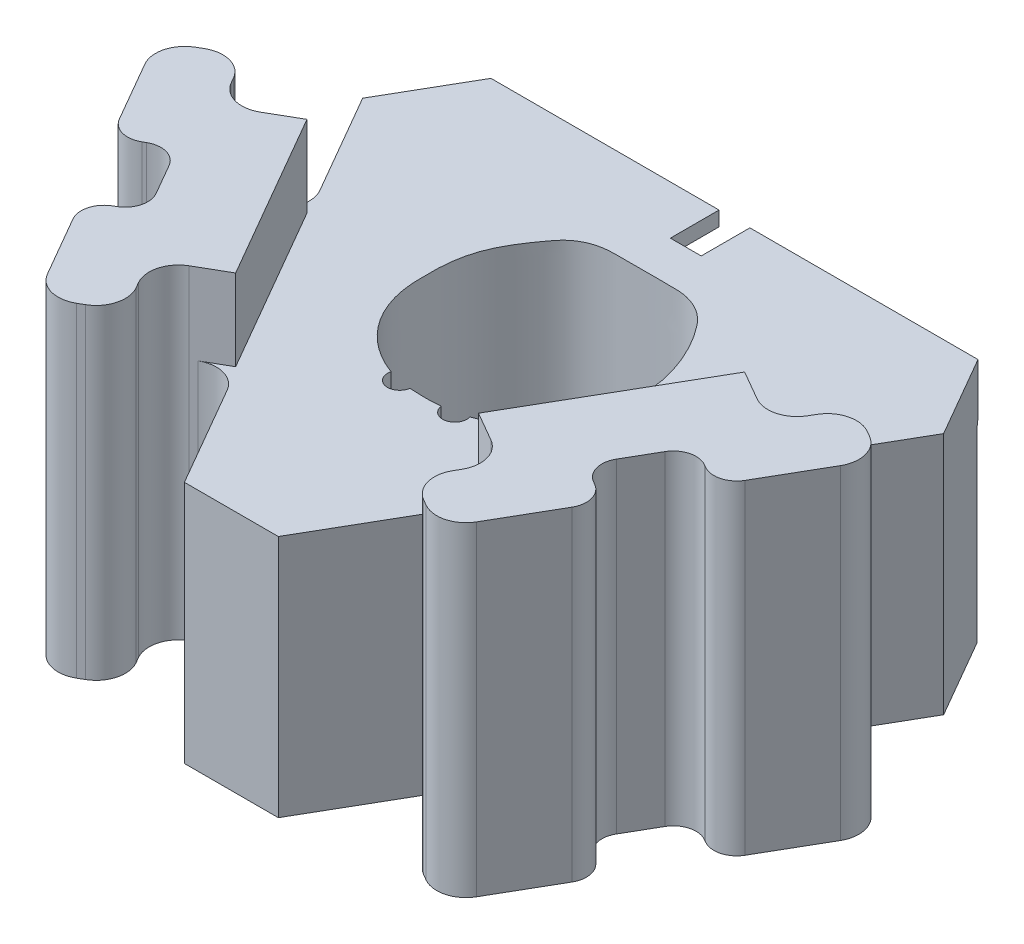
SolidWorks part; units mm, degrees
material "Nylon 101"
ref_plane "Plan de face" through (0, 0, 0) normal (0, 0, 1) x (1, 0, 0)
ref_plane "Plan de dessus" through (0, 0, 0) normal (0, 1, 0) x (1, 0, 0)
ref_plane "Plan de droite" through (0, 0, 0) normal (1, 0, 0) x (0, 0, -1)
sketch "Esquisse2" plane through (0, 0, 0) normal (0, 1, 0) x (1, 0, 0)
  line L5 (0, 0) -> (0, 12) construction
  line L6 (15, 12) -> (-15, 12)
  line L10 (2.8923, -18.9904) -> (17.8923, 6.9904)
  line L11 (0, 0) -> (10.3923, -6) construction
  line L12 (-17.8923, 6.9904) -> (-2.8923, -18.9904)
  line L13 (0, 0) -> (-10.3923, -6) construction
  line L14 (-15, 12) -> (-17.8923, 6.9904)
  line L15 (-2.8923, -18.9904) -> (2.8923, -18.9904)
  line L16 (17.8923, 6.9904) -> (15, 12)
  circle A0 centre (0, 0) radius 6.4543 construction
  spline S0 degree 3 poles (-6.4916, -0.6583) (-6.5698, 2.1101) (-5.6306, 3.6458) (-3.9015, 5.9899) (-2.756, 6.4428) (-0.8765, 6.4556) (1.1323, 6.4563) (2.7646, 6.4372) (3.9155, 5.9368) (5.686, 3.7258) (6.557, 1.3673) (6.4965, -0.4633) (6.5146, -1.1319) (6.2478, -3.8936) (4.3275, -6.6394) (0.5445, -7.077) (-0.4227, -7.0644) (-3.089, -6.9353) (-6.1206, -4.861) (-6.5148, -1.2298) (-6.4916, -0.6583) (-6.5698, 2.1101) (-5.6306, 3.6458) knots -0.028087 -0.008777 -0.000975 0 0.112372 0.130276 0.173621 0.187169 0.252205 0.26694 0.319781 0.34342 0.479691 0.498677 0.514296 0.542967 0.756721 0.785787 0.80456 0.825241 0.971913 0.991223 0.999025 1 1.112372 1.130276 1.173621 only from (-6.4978, -0.4355) to (-6.4978, -0.4355)
  point P6 (0, 12)
  point P15 (0, 0)
  dimension "D1" = 30
  dimension "D2" = 3
  dimension "D3" = 12
extrude "Boss.-Extru.1" add sketch "Esquisse2" along normal blind 15
sketch "Esquisse3" plane through (0, 0, 0) normal (0, 1, 0) x (1, 0, 0)
  line L0 (0, 0) -> (3.3, 0) construction
  line L1 (0, 0) -> (0, 3.3) construction
  line L2 (-16.4462, 9.4952) -> (0, 0) construction
  line L5 (-17.8923, 6.9904) -> (-15, 12) construction
  line L6 (0, 0) -> (16.4462, 9.4952) construction
  line L7 (15, 12) -> (17.8923, 6.9904) construction
  line L8 (0, 0) -> (0, -18.9904) construction
  line L9 (2.8923, -18.9904) -> (-2.8923, -18.9904) construction
  circle A0 centre (0, 0) radius 3.3 construction
  circle A5 centre (-12.9821, 7.4952) radius 2
  circle A7 centre (12.9821, 7.4952) radius 2
  circle A8 centre (0, -14.9904) radius 2
  point P23 (0, 0)
  dimension "D1" = 6.6
  dimension "D3" = 4
  dimension "D2" = 4
  dimension "D4" = 3
extrude "Enlèv. mat.-Extru.3" [suppressed] cut sketch "Esquisse3" against normal blind 8 and the other way through all from surface
sketch "Esquisse4" plane through (0, 0, 0) normal (0, 0, 1) x (1, 0, 0)
  line L0 (0, 0) -> (0, 7) construction
  line L1 (11, 3) -> (-11, 3) construction
  line L2 (11, 3) -> (11, 11) construction
  line L3 (11, 11) -> (-11, 11) construction
  line L4 (-11, 3) -> (-11, 11) construction
  line L5 (11, 3) -> (-11, 11) construction
  line L6 (11, 11) -> (-11, 3) construction
  line L8 (-17.8923, 0) -> (-2.8923, 0) construction
  circle A0 centre (-11, 11) radius 1.5
  circle A1 centre (11, 11) radius 1.5
  circle A2 centre (11, 3) radius 1.5
  circle A3 centre (-11, 3) radius 1.5
  point P0 (0, 7)
  dimension "D4" = 3
  dimension "D1" = 8
  dimension "D2" = 22
  dimension "D3" = 3
extrude "Enlèv. mat.-Extru.4" cut sketch "Esquisse4" along normal blind 8 from surface starting at face at (0, 7.5, -12)
sketch "Esquisse5" plane through (0, 0, 0) normal (0, 1, 0) x (1, 0, 0)
  line L0 (0, 0) -> (0, -18.9904) construction
  line L1 (2.8923, -18.9904) -> (-2.8923, -18.9904) construction
  line L2 (10.3923, -6) -> (17.3205, -10) construction
  line L3 (17.8923, 6.9904) -> (2.8923, -18.9904) construction
  line L4 (13.2205, -17.1014) -> (15.3705, -13.3775)
  line L5 (20.7617, -0.4397) -> (20.4153, -0.2397)
  line L6 (17.9564, -0.8986) -> (17.7564, -1.245)
  line L7 (15.2976, -1.9038) -> (13.3923, -0.8038)
  line L8 (13.3923, -0.8038) -> (7.3923, -11.1962)
  line L9 (9.2976, -12.2962) -> (7.3923, -11.1962)
  line L10 (9.7564, -15.1014) -> (9.9564, -14.755)
  line L11 (10.7617, -17.7603) -> (10.4153, -17.5603)
  line L12 (20.7617, -0.4397) -> (20.4153, -0.2397)
  line L13 (17.9564, -0.8986) -> (17.7564, -1.245)
  line L14 (15.2976, -1.9038) -> (13.3923, -0.8038)
  line L15 (9.2976, -12.2962) -> (7.3923, -11.1962)
  line L16 (9.7564, -15.1014) -> (9.9564, -14.755)
  line L17 (10.7617, -17.7603) -> (10.4153, -17.5603)
  line L18 (-17.3205, -10) -> (-18.5705, -7.8349) construction
  line L19 (-16.0705, -12.1651) -> (-17.3205, -10) construction
  line L20 (-10.3923, -6) -> (-17.3205, -10) construction
  line L21 (-19.2705, -6.6225) -> (-21.4205, -2.8986)
  line L22 (-17.1849, -7.0349) -> (-17.3581, -7.1349)
  line L23 (-14.1724, -9.4526) -> (-15.2724, -7.5474)
  line L24 (-14.8581, -11.4651) -> (-14.6849, -11.3651)
  line L25 (-10.7617, -17.7603) -> (-10.4153, -17.5603)
  line L26 (-9.7564, -15.1014) -> (-9.9564, -14.755)
  line L27 (-9.2976, -12.2962) -> (-7.3923, -11.1962)
  line L28 (-15.2976, -1.9038) -> (-13.3923, -0.8038)
  line L29 (-17.9564, -0.8986) -> (-17.7564, -1.245)
  line L30 (-20.7617, -0.4397) -> (-20.4153, -0.2397)
  line L31 (-10.7617, -17.7603) -> (-10.4153, -17.5603)
  line L32 (-9.7564, -15.1014) -> (-9.9564, -14.755)
  line L33 (14.8581, -11.4651) -> (14.6849, -11.3651)
  line L34 (14.1724, -9.4526) -> (15.2724, -7.5474)
  line L35 (17.1849, -7.0349) -> (17.3581, -7.1349)
  line L36 (16.0705, -12.1651) -> (17.3205, -10) construction
  line L37 (19.2705, -6.6225) -> (21.4205, -2.8986)
  line L38 (17.3205, -10) -> (18.5705, -7.8349) construction
  line L39 (-9.2976, -12.2962) -> (-7.3923, -11.1962)
  line L40 (-13.3923, -0.8038) -> (-7.3923, -11.1962)
  line L41 (-15.2976, -1.9038) -> (-13.3923, -0.8038)
  line L42 (-17.9564, -0.8986) -> (-17.7564, -1.245)
  line L43 (-20.7617, -0.4397) -> (-20.4153, -0.2397)
  line L44 (-13.2205, -17.1014) -> (-15.3705, -13.3775)
  arc A0 (10.7617, -17.7603) -> (13.2205, -17.1014) centre (11.6617, -16.2014) ccw
  arc A1 (9.7564, -15.1014) -> (10.4153, -17.5603) centre (11.3153, -16.0014) ccw
  arc A2 (9.2976, -12.2962) -> (9.9564, -14.755) centre (8.3976, -13.855) cw
  arc A3 (21.4205, -2.8986) -> (20.7617, -0.4397) centre (19.8617, -1.9986) ccw
  arc A4 (17.7564, -1.245) -> (15.2976, -1.9038) centre (16.1976, -0.345) cw
  arc A5 (20.4153, -0.2397) -> (17.9564, -0.8986) centre (19.5153, -1.7986) ccw
  arc A6 (10.4153, -17.5603) -> (9.7564, -15.1014) centre (11.3153, -16.0014) cw
  arc A7 (9.9564, -14.755) -> (9.2976, -12.2962) centre (8.3976, -13.855) ccw
  arc A8 (13.2205, -17.1014) -> (10.7617, -17.7603) centre (11.6617, -16.2014) cw
  arc A9 (15.2976, -1.9038) -> (17.7564, -1.245) centre (16.1976, -0.345) ccw
  arc A10 (17.9564, -0.8986) -> (20.4153, -0.2397) centre (19.5153, -1.7986) cw
  arc A11 (20.7617, -0.4397) -> (21.4205, -2.8986) centre (19.8617, -1.9986) cw
  arc A24 (17.3581, -7.1349) -> (19.2705, -6.6225) centre (18.0581, -5.9225) ccw
  arc A25 (15.2724, -7.5474) -> (17.1849, -7.0349) centre (16.4849, -8.2474) cw
  arc A26 (14.6849, -11.3651) -> (14.1724, -9.4526) centre (15.3849, -10.1526) cw
  arc A27 (14.8581, -11.4651) -> (15.3705, -13.3775) centre (14.1581, -12.6775) cw
  arc A28 (-14.8581, -11.4651) -> (-15.3705, -13.3775) centre (-14.1581, -12.6775) ccw
  arc A29 (-14.6849, -11.3651) -> (-14.1724, -9.4526) centre (-15.3849, -10.1526) ccw
  arc A30 (-15.2724, -7.5474) -> (-17.1849, -7.0349) centre (-16.4849, -8.2474) ccw
  arc A31 (-17.3581, -7.1349) -> (-19.2705, -6.6225) centre (-18.0581, -5.9225) cw
  arc A32 (-20.7617, -0.4397) -> (-21.4205, -2.8986) centre (-19.8617, -1.9986) ccw
  arc A33 (-17.9564, -0.8986) -> (-20.4153, -0.2397) centre (-19.5153, -1.7986) ccw
  arc A34 (-15.2976, -1.9038) -> (-17.7564, -1.245) centre (-16.1976, -0.345) cw
  arc A35 (-13.2205, -17.1014) -> (-10.7617, -17.7603) centre (-11.6617, -16.2014) ccw
  arc A36 (-9.9564, -14.755) -> (-9.2976, -12.2962) centre (-8.3976, -13.855) cw
  arc A37 (-10.4153, -17.5603) -> (-9.7564, -15.1014) centre (-11.3153, -16.0014) ccw
  arc A38 (-20.4153, -0.2397) -> (-17.9564, -0.8986) centre (-19.5153, -1.7986) cw
  arc A39 (-17.7564, -1.245) -> (-15.2976, -1.9038) centre (-16.1976, -0.345) ccw
  arc A40 (-21.4205, -2.8986) -> (-20.7617, -0.4397) centre (-19.8617, -1.9986) cw
  arc A41 (-9.2976, -12.2962) -> (-9.9564, -14.755) centre (-8.3976, -13.855) ccw
  arc A42 (-9.7564, -15.1014) -> (-10.4153, -17.5603) centre (-11.3153, -16.0014) cw
  arc A43 (-10.7617, -17.7603) -> (-13.2205, -17.1014) centre (-11.6617, -16.2014) cw
  point P19 (12.3205, -18.6603)
  point P22 (8.8564, -16.6603)
  point P25 (10.8564, -13.1962)
  point P28 (22.3205, -1.3397)
  point P31 (16.8564, -2.8038)
  point P34 (18.8564, 0.6603)
  point P64 (14.7224, -8.5)
  point P72 (15.9724, -6.3349)
  point P75 (13.4724, -10.6651)
  point P88 (-13.4724, -10.6651)
  point P89 (-15.9724, -6.3349)
  point P90 (-18.8564, 0.6603)
  point P91 (-16.8564, -2.8038)
  point P92 (-22.3205, -1.3397)
  point P93 (-10.8564, -13.1962)
  point P94 (-8.8564, -16.6603)
  point P95 (-12.3205, -18.6603)
  dimension "D5" = 1.8
  dimension "D8" = 1.4
  dimension "D1" = 8
  dimension "D2" = 4
  dimension "D3" = 4
  dimension "D4" = 10
  dimension "D6" = 3
  dimension "D7" = 5
extrude "Boss.-Extru.2" add sketch "Esquisse5" against normal up to surface and the other way blind 5 from surface contours L5 A5 L6 A4 L7 L8 L9 A2 L10 A1 L11 A0 L4 A3 | L25 A37 L26 A36 L27 L40 L28 A34 L29 A33 L30 A32 L21 A31 L22 A30 L23 A29 L24 A28 L44 A35 region at (13.999, 0, 8.0823) region at (-13.999, 0, 8.0823) up to face at (0, 0, 0) starting at face at (0, 15, 0)
fillet "Congé5" radius 1.8 4 edges at (13.3923, 7.5, 0.8038) (7.3923, 7.5, 11.1962) (-7.3923, 7.5, 11.1962) (-13.3923, 7.5, 0.8038)
sketch "Esquisse6" plane through (0, 0, 0) normal (0, 1, 0) x (1, 0, 0)
  line L0 (-13.3923, -0.8038) -> (-7.3923, -11.1962)
  line L1 (-7.3923, -11.1962) -> (-7.4789, -11.2462)
  line L2 (-7.3923, -11.1962) -> (-9.2976, -12.2962) construction
  line L3 (-7.4789, -11.2462) -> (-13.4789, -0.8538)
  line L4 (-13.3923, -0.8038) -> (-15.2976, -1.9038) construction
  line L5 (-13.4789, -0.8538) -> (-13.3923, -0.8038)
  line L6 (7.3923, -11.1962) -> (13.3923, -0.8038)
  line L7 (13.3923, -0.8038) -> (13.4789, -0.8538)
  line L8 (14.9512, -1.7038) -> (13.3923, -0.8038) construction
  line L9 (13.4789, -0.8538) -> (7.4789, -11.2462)
  line L10 (7.3923, -11.1962) -> (9.2976, -12.2962) construction
  line L11 (7.4789, -11.2462) -> (7.3923, -11.1962)
  dimension "D1" = 0.1
  dimension "D2" = 0.1
extrude "Enlèv. mat.-Extru.5" cut sketch "Esquisse6" along normal up to surface (20 mm away) from surface up to face at (-14.8463, 20, 8.5715) starting at face at (0, 15, 4.1586)
sketch "Esquisse7" plane through (0, 0, -12) normal (0, 0, -1) x (-1, 0, 0)
  line L0 (15, 15) -> (15, 0) construction
  line L1 (-15, 0) -> (15, 0) construction
  line L2 (-15, 0) -> (-15, 14) construction
  line L3 (-15, 14) -> (-0.85, 14) construction
  line L4 (15, 0) -> (15, 14) construction
  line L5 (-15, 15) -> (15, 15) construction
  line L6 (0.85, 0) -> (-0.85, 0)
  line L7 (0.85, 14) -> (0.85, 15) construction
  line L8 (0.85, 15) -> (-0.85, 15) construction
  line L9 (-0.85, 14) -> (-0.85, 15) construction
  line L10 (-0.85, 0) -> (-0.85, 14) construction
  line L11 (0.85, 0) -> (0.85, 14) construction
  line L12 (-0.85, 14) -> (0.85, 14) construction
  line L13 (0.85, 14) -> (15, 14) construction
  line L14 (-15.1, -0.1) -> (-15.1, 14.1)
  line L15 (-15.1, 14.1) -> (-0.95, 14.1)
  line L16 (-0.95, 14.1) -> (-0.95, 15.1)
  line L17 (0.95, 15.1) -> (-0.95, 15.1)
  line L18 (0.95, 14.1) -> (0.95, 15.1)
  line L19 (0.95, 14.1) -> (15.1, 14.1)
  line L20 (15.1, -0.1) -> (15.1, 14.1)
  line L21 (-15.1, -0.1) -> (15.1, -0.1)
  circle A0 centre (11, 11) radius 1.5 construction
  circle M9 centre (-11, 3) radius 1.5
  circle M10 centre (11, 11) radius 1.5
  circle M11 centre (11, 3) radius 1.5
  circle M12 centre (-11, 11) radius 1.5
  line M13 (-15, 0) -> (15, 0)
  line M14 (15, 0) -> (15, 15)
  line M15 (15, 15) -> (-15, 15)
  line M16 (-15, 15) -> (-15, 0)
  dimension "D1" = 3
  dimension "D2" = 0.85
  dimension "D3" = 0.85
  dimension "D4" = 0.1
extrude "Enlèv. mat.-Extru.6" cut sketch "Esquisse7" against normal blind 3 contours L14 L21 L20 L19 L15 M14 M13 M16 | L19 L18 L16 L15 M15 M16 M13 M14 M10 M12 M11 M9 | L18 L17 L16 M15 region at (-7.925, -0.0334, -12) region at (0, 7.0859, -12) region at (0, 15.05, -12)
fillet "Congé6" radius 3 2 edges at (-15.1, 14.1, -10.4134) (15.1, 14.1, -10.4134)
sketch "Esquisse8" plane through (0, 15, 0) normal (0, 1, 0) x (1, 0, 0)
  line L0 (0, 0) -> (0, -2.8854) construction
  circle A0 centre (-1.7, -6.9242) radius 0.75
  circle A1 centre (1.7, -6.9242) radius 0.75
  spline S0 degree 3 poles (-5.6306, 3.6458) (-6.5698, 2.1101) (-6.4916, -0.6583) (-6.5148, -1.2298) (-6.1206, -4.861) (-3.089, -6.9353) (-0.4227, -7.0644) (0.5445, -7.077) (4.3275, -6.6394) (6.2478, -3.8936) (6.5146, -1.1319) (6.4965, -0.4633) (6.557, 1.3673) (5.686, 3.7258) (3.9155, 5.9368) (2.7646, 6.4372) (1.1323, 6.4563) (-0.8765, 6.4556) (-2.756, 6.4428) (-3.9015, 5.9899) (-5.6306, 3.6458) (-6.5698, 2.1101) (-6.4916, -0.6583) knots -0.173621 -0.130276 -0.112372 0 0.000975 0.008777 0.028087 0.174759 0.19544 0.214213 0.243279 0.457033 0.485704 0.501323 0.520309 0.65658 0.680219 0.73306 0.747795 0.812831 0.826379 0.869724 0.887628 1 1.000975 1.008777 1.028087 only from (-6.4978, -0.4355) to (-6.4978, -0.4355) construction
  point P2 (0, 0)
  dimension "D2" = 1.5
  dimension "D1" = 1.7
extrude "Enlèv. mat.-Extru.7" cut sketch "Esquisse8" against normal through all
